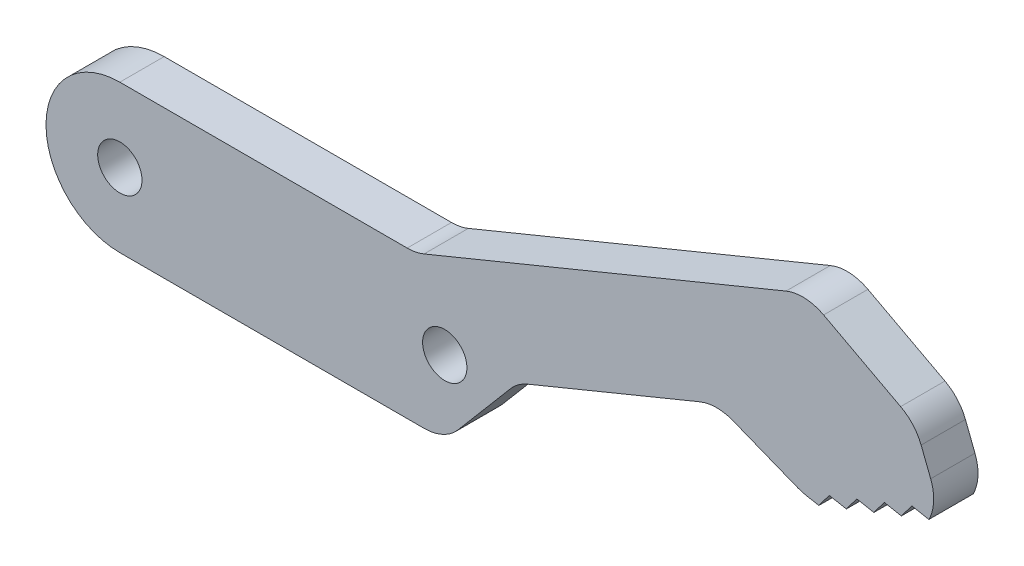
SolidWorks part; units mm, degrees
ref_plane "Front Plane" through (0, 0, 0) normal (0, 0, 1) x (1, 0, 0)
ref_plane "Top Plane" through (0, 0, 0) normal (0, 1, 0) x (1, 0, 0)
ref_plane "Right Plane" through (0, 0, 0) normal (1, 0, 0) x (0, 0, -1)
sketch "Sketch1" plane through (0, 0, 0) normal (0, 0, 1) x (1, 0, 0)
  line L0 (-9.7336, 0) -> (12.2664, 0) construction
  line L3 (-9.7336, 5) -> (12.2664, 5)
  line L4 (-9.7336, -5) -> (12.2664, -5)
  line L9 (10.3164, 5) -> (14.0831, -4.6583) construction
  line L10 (10.3164, 5) -> (41.7622, 17.929) construction
  line L11 (14.0831, -4.6583) -> (45.7541, 7.6934) construction
  line L12 (41.7622, 17.929) -> (45.7541, 7.6934) construction
  line L13 (10.3164, 5) -> (36.6754, 15.8375)
  line L14 (36.6754, 15.8375) -> (44.119, 11.8859)
  line L15 (44.119, 11.8859) -> (45.7541, 7.6934)
  line L16 (45.7541, 7.6934) -> (36.4376, 4.06)
  line L17 (30.6614, 6.3527) -> (17.1991, 0.8177)
  line L18 (36.4376, 4.06) -> (30.6614, 6.3527)
  line L19 (36.4376, 4.06) -> (37.5963, 3.841)
  line L20 (37.5963, 3.841) -> (38.3009, 4.7867)
  line L21 (37.5963, 3.841) -> (45.0495, 6.7478) construction
  line L22 (38.3009, 4.7867) -> (39.4596, 4.5677)
  line L23 (39.4596, 4.5677) -> (40.1642, 5.5133)
  line L24 (40.1642, 5.5133) -> (41.3229, 5.2944)
  line L25 (41.3229, 5.2944) -> (42.0275, 6.24)
  line L26 (42.0275, 6.24) -> (43.1862, 6.0211)
  line L27 (43.1862, 6.0211) -> (43.8908, 6.9667)
  line L28 (43.8908, 6.9667) -> (45.0495, 6.7478)
  line L29 (45.0495, 6.7478) -> (45.7541, 7.6934)
  line L30 (17.1991, 0.8177) -> (12.2664, -5)
  arc A2 (-9.7336, 5) -> (-9.7336, -5) centre (-9.7336, 0) ccw
  arc A3 (12.2664, -5) -> (12.2664, 5) centre (12.2664, 0) ccw
  circle A4 centre (-9.7336, 0) radius 1.5
  circle A6 centre (12.2664, 0) radius 1.5
  point P3 (1.2664, 0)
  dimension "D3" = 3
  dimension "D1" = 22
  dimension "D2" = 10
  dimension "D4" = 1.95
  dimension "D5" = 157.65
  dimension "D6" = 34
  dimension "D7" = 5.5
  dimension "D8" = 4.5
  dimension "D9" = 10
  dimension "D10" = 136
  dimension "D11" = 2
  dimension "D12" = 0.625
  dimension "D13" = 8
  dimension "D14" = 2
  dimension "D15" = 2
  dimension "D16" = 2
  dimension "D17" = 2
extrude "Boss-Extrude2" add sketch "Sketch1" along normal blind 3 contours A3 L3 A2 L4 A6 A4 | A3 L17 L18 L16 L15 L14 L13 L3 | L19 L20 L16 | L22 L23 L16 | L24 L25 L16 | L26 L27 L16 | L28 L29 L16 region at (0.7896, 0.0869, 0) region at (30.4221, 8.4012, 0) region at (44.8981, 7.136, 0) region at (37.4449, 4.2292, 0) region at (43.0348, 6.4093, 0) region at (39.3082, 4.9559, 0) region at (41.1715, 5.6826, 0)
fillet "Fillet4" radius 3 6 edges at (30.6614, 6.3527, 1.5) (36.4376, 4.06, 1.5) (45.7541, 7.6934, 1.5) (44.119, 11.8859, 1.5) (36.6754, 15.8375, 1.5) (10.3164, 5, 1.5) first distance on face at (23.9302, 3.5852, 1.5) first distance on face at (33.5495, 5.2064, 1.5) first distance on face at (45.4018, 7.2206, 1.5) first distance on face at (44.9366, 9.7896, 1.5) first distance on face at (40.3972, 13.8617, 1.5) first distance on face at (23.4959, 10.4188, 1.5)
fillet "Fillet5" radius 3 2 edges at (12.2664, -5, 1.5) (17.1991, 0.8177, 1.5) first distance on face at (1.2664, -5, 1.5) first distance on face at (14.7327, -2.0911, 1.5)
